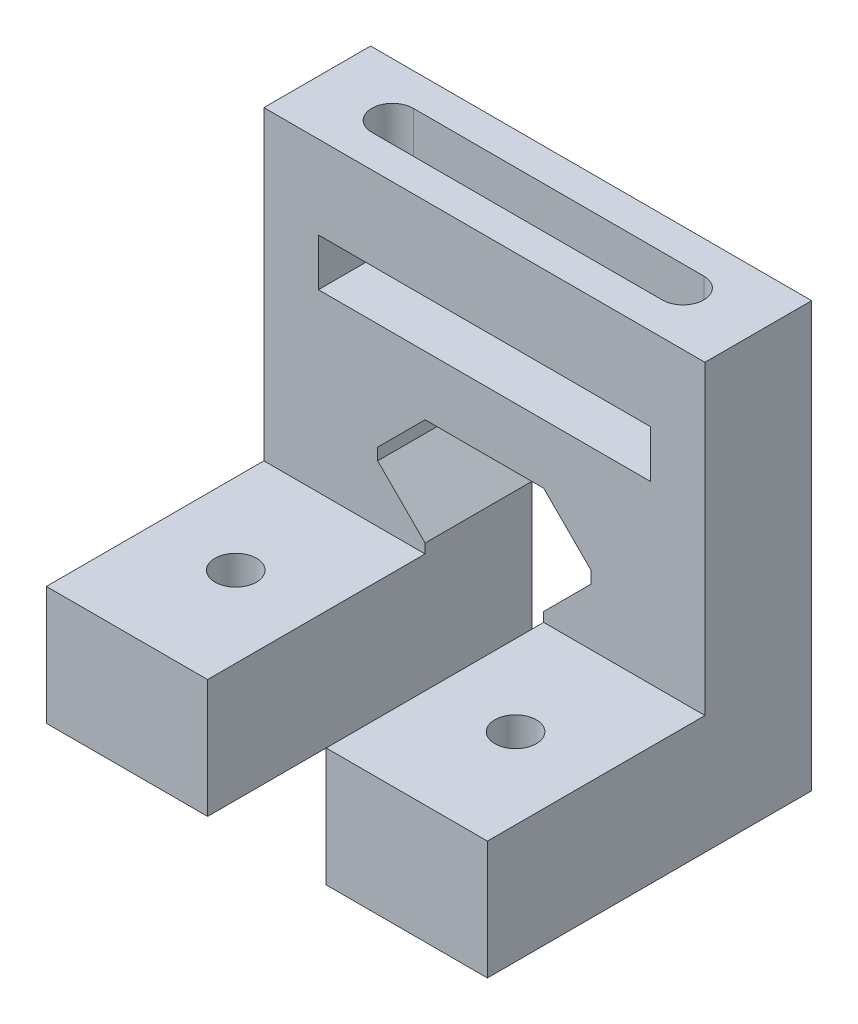
SolidWorks part; units mm, degrees
ref_plane "Front Plane" through (0, 0, 0) normal (0, 0, 1) x (1, 0, 0)
ref_plane "Top Plane" through (0, 0, 0) normal (0, 1, 0) x (1, 0, 0)
ref_plane "Right Plane" through (0, 0, 0) normal (1, 0, 0) x (0, 0, -1)
sketch "Sketch1" plane through (0, 0, 0) normal (0, 1, 0) x (1, 0, 0)
  line L0 (13.6, 13.6725) -> (18.6, 13.6725) construction
  line L1 (0, 0) -> (13.6, 0)
  line L2 (0, 0) -> (0, 27.345)
  line L3 (0, 27.345) -> (13.6, 27.345)
  line L4 (13.6, 0) -> (13.6, 27.345)
  line L5 (18.6, 13.6725) -> (18.6, 22.9985) construction
  line L6 (37.2, 27.345) -> (23.6, 27.345)
  line L7 (23.6, 0) -> (23.6, 27.345)
  line L8 (37.2, 0) -> (23.6, 0)
  line L9 (37.2, 0) -> (37.2, 27.345)
  dimension "D1" = 13.6
  dimension "D2" = 27.345
  dimension "D3" = 5
extrude "Boss-Extrude1" add sketch "Sketch1" along normal blind 10
sketch "Sketch2" plane through (0, 0, -27.345) normal (0, 0, -1) x (-1, 0, 0)
  line L0 (-37.2, 10) -> (-31.1, 22)
  line L1 (-31.1, 22) -> (-31.1, 35.8)
  line L2 (-31.1, 35.8) -> (-6.1, 35.8)
  line L3 (-23.6, 10) -> (-23.6, 19.8)
  line L4 (-23.6, 19.8) -> (-13.6, 19.8)
  line L5 (-18.6, 19.8) -> (-18.6, 35.8) construction
  line L6 (-6.1, 22) -> (-6.1, 35.8)
  line L7 (-13.6, 10) -> (-13.6, 19.8)
  line L8 (0, 10) -> (-6.1, 22)
  line L9 (-37.2, 10) -> (-23.6, 10)
  line L10 (-13.6, 10) -> (0, 10)
  line L12 (-31.1, 35.8) -> (-37.2, 35.8)
  line L13 (-31.1, 35.8) -> (-31.1, 10)
  line L14 (-31.1, 10) -> (-37.2, 10)
  line L15 (-37.2, 35.8) -> (-37.2, 10)
  line L16 (-6.1, 35.8) -> (0, 35.8)
  line L17 (-6.1, 35.8) -> (-6.1, 10)
  line L18 (-6.1, 10) -> (0, 10)
  line L19 (0, 35.8) -> (0, 10)
  dimension "D1" = 12
  dimension "D2" = 6.1
  dimension "D3" = 16
  dimension "D4" = 25.8
  dimension "D5" = 5
extrude "Boss-Extrude2" add sketch "Sketch2" against normal blind 9 contours L1 L2 L6 L8 L10 L7 L4 L3 L9 L0 | L13 L12 L15 L14 | L17 L16 L19 L18
sketch "Sketch3" plane through (0, 10, 0) normal (0, 1, 0) x (1, 0, 0)
  line L0 (23.6, 0) -> (37.2, 0) construction
  line L1 (37.2, 0) -> (37.2, 18.345) construction
  line L2 (18.6, 18.345) -> (18.6, 5.4963) construction
  line L3 (37.2, 18.345) -> (0, 18.345) construction
  circle A0 centre (30.4, 9.1725) radius 1.75
  circle A1 centre (6.8, 9.1725) radius 1.75
  point P4 (30.4, 0)
  point P7 (37.2, 9.1725)
  dimension "D1" = 3.5
extrude "Cut-Extrude1" cut sketch "Sketch3" against normal through all
sketch "Sketch5" plane through (0, 35.8, 0) normal (0, 1, 0) x (1, 0, 0)
  line L0 (6.35, 22.845) -> (30.85, 22.845) construction
  line L1 (6.35, 24.595) -> (30.85, 24.595)
  line L2 (6.35, 21.095) -> (30.85, 21.095)
  line L3 (0, 18.345) -> (0, 27.345) construction
  line L4 (37.2, 27.345) -> (0, 27.345) construction
  arc A0 (6.35, 24.595) -> (6.35, 21.095) centre (6.35, 22.845) ccw
  arc A1 (30.85, 21.095) -> (30.85, 24.595) centre (30.85, 22.845) ccw
  point P2 (18.6, 22.845)
  point P9 (0, 22.845)
  point P12 (18.6, 27.345)
  dimension "D1" = 3.5
  dimension "D2" = 24.5
sketch "Sketch6" plane through (0, 0, -27.345) normal (0, 0, -1) x (-1, 0, 0)
  line L0 (-30.85, 35.8) -> (-32.6, 35.8) construction
  line L1 (-32.6, 24.8) -> (-4.6, 24.8)
  line L2 (-32.6, 24.8) -> (-32.6, 28.8)
  line L3 (-32.6, 28.8) -> (-4.6, 28.8)
  line L4 (-4.6, 24.8) -> (-4.6, 28.8)
  point P4 (-18.6, 28.8)
  dimension "D1" = 4
  dimension "D2" = 28
  dimension "D3" = 7
extrude "Cut-Extrude2" cut sketch "Sketch6" against normal through all
extrude "Cut-Extrude3" cut sketch "Sketch5" against normal up to next contours L2 A1 L1 A0
sketch "Sketch8" plane through (0, 0, -18.345) normal (0, 0, 1) x (1, 0, 0)
  line L0 (23.6, 19.8) -> (13.6, 19.8) construction
  line L1 (9.6, 19.8) -> (27.6, 19.8)
  line L2 (9.6, 19.8) -> (9.6, 14.8)
  line L3 (9.6, 14.8) -> (27.6, 14.8)
  line L4 (27.6, 19.8) -> (27.6, 14.8)
  line L5 (32.6, 28.8) -> (4.6, 28.8) construction
  point P8 (18.6, 28.8)
  point P9 (18.6, 19.8)
  dimension "D1" = 5
  dimension "D2" = 18
extrude "Cut-Extrude4" cut sketch "Sketch8" against normal up to next contours L3 L4 L1 L2
chamfer "Chamfer2" distance 4 angle 45 4 edges at (27.6, 19.8, -22.845) (23.6, 14.8, -22.845) (13.6, 14.8, -22.845) (9.6, 19.8, -22.845)
